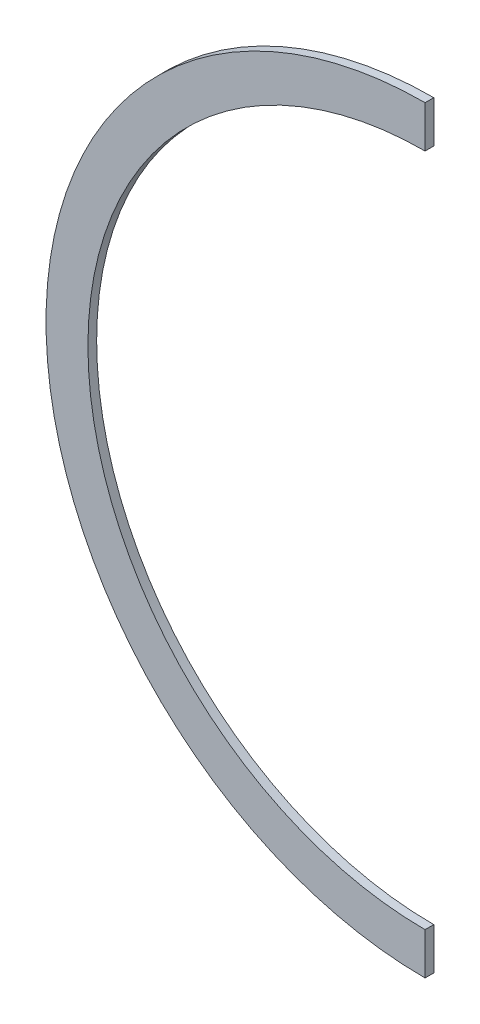
SolidWorks part; units mm, degrees
material "Balsa"
ref_plane "Front Plane" through (0, 0, 0) normal (0, 0, 1) x (1, 0, 0)
ref_plane "Top Plane" through (0, 0, 0) normal (0, 1, 0) x (1, 0, 0)
ref_plane "Right Plane" through (0, 0, 0) normal (1, 0, 0) x (0, 0, -1)
sketch "Sketch1" plane through (0, 0, 0) normal (0, 0, 1) x (1, 0, 0)
  line L0 (0, 0) -> (0, 499.9473) construction
  line L1 (0, -114.7984) -> (0, -129.4545) construction
  line L2 (0, -374.4718) -> (0, 404.2655) construction
  line L3 (-1.651, 142.9921) -> (-1.651, 150.6121) construction
  line L4 (1.651, 142.9921) -> (1.651, 150.6121) construction
  line L5 (-1.651, 142.9921) -> (1.651, 142.9921) construction
  line L6 (136.2041, -53.806) -> (0.0002, 24.7625) construction
  line L7 (-136.2076, -53.7991) -> (0.0002, 24.7625) construction
  line L8 (136.2041, -53.806) -> (0.0002, 24.7625) construction
  line L9 (-136.2076, -53.7991) -> (0.0002, 24.7625) construction
  line L10 (-125.0584, -45.4626) -> (-118.4576, -41.6554) construction
  line L11 (-123.6259, -48.4483) -> (-116.8078, -44.5157) construction
  line L12 (-118.4576, -41.6554) -> (-116.8078, -44.5157) construction
  line L13 (-124.1455, -48.7479) -> (-123.6847, -48.4822) construction
  line L14 (-123.6847, -48.4822) -> (-123.6259, -48.4483) construction
  line L15 (-125.7952, -45.8876) -> (-125.1113, -45.4931) construction
  line L16 (-125.1113, -45.4931) -> (-125.0584, -45.4626) construction
  line L17 (125.4797, -45.7137) -> (125.1075, -45.499) construction
  line L18 (123.8298, -48.5739) -> (123.6807, -48.488) construction
  line L19 (117.0223, -44.647) -> (118.6722, -41.7868) construction
  line L20 (123.6807, -48.488) -> (123.6228, -48.4545) construction
  line L21 (123.6228, -48.4545) -> (117.0223, -44.647) construction
  line L22 (125.1075, -45.499) -> (125.0554, -45.4689) construction
  line L23 (125.0554, -45.4689) -> (118.6722, -41.7868) construction
  line L24 (-107.079, -46.8884) -> (-120.3798, -54.5735)
  line L25 (-108.6638, -44.1348) -> (-121.9647, -51.8199)
  line L28 (-115.4206, -47.9666) -> (-121.9445, -51.7361) construction
  line L29 (-120.2754, -54.5131) -> (-108.646, -44.1245) construction
  line L30 (-114.4607, -49.3188) -> (-122.1124, -53.7399) construction
  line L31 (-113.7686, -50.8257) -> (-120.3665, -54.6379) construction
  line L32 (-115.4206, -47.9666) -> (-113.7686, -50.8257) construction
  line L33 (106.3137, -46.4532) -> (129.9098, -60.0883)
  line L34 (107.9004, -43.7007) -> (131.505, -57.3407)
  line L35 (129.9098, -60.0883) -> (131.505, -57.3407)
  line L36 (129.9098, -60.0883) -> (131.505, -57.3407) construction
  line L37 (107.9004, -43.7007) -> (131.505, -57.3407) construction
  line L38 (106.3137, -46.4532) -> (129.9098, -60.0883) construction
  line L39 (129.9098, -60.0883) -> (107.9004, -43.7007) construction
  line L40 (118.9051, -51.8945) -> (101.8722, -42.0519) construction
  line L41 (120.3631, -54.6438) -> (113.7655, -50.8313)
  line L42 (122.0152, -51.7848) -> (122.0057, -51.7794) construction
  line L43 (113.7655, -50.8313) -> (115.4176, -47.9723)
  line L44 (122.0057, -51.7794) -> (121.9413, -51.7421) construction
  line L45 (121.9413, -51.7421) -> (115.4176, -47.9723)
  line L46 (-108.6638, -44.1348) -> (-121.9647, -51.8199)
  line L47 (-107.079, -46.8884) -> (-120.3798, -54.5735)
  arc A0 (-1.651, 150.6121) -> (-125.0584, -45.4626) centre (0, 12.7) ccw
  circle A1 centre (0, 12.7) radius 120.904
  arc A2 (0, 150.622) -> (-1.651, 150.6121) centre (0, 12.7) ccw
  circle A3 centre (0, 12.7) radius 137.922 construction
  arc A4 (1.651, 150.6121) -> (0, 150.622) centre (0, 12.7) ccw
  arc A5 (-124.3508, -46.9604) -> (-123.6259, -48.4483) centre (0, 12.7) ccw
  arc A6 (-123.6259, -48.4483) -> (-121.9445, -51.7361) centre (0, 12.7) ccw
  arc A7 (-125.0584, -45.4626) -> (-124.3508, -46.9604) centre (0, 12.7) ccw
  arc A8 (124.3477, -46.9667) -> (125.0554, -45.4689) centre (0, 12.7) ccw
  arc A9 (125.0554, -45.4689) -> (1.651, 150.6121) centre (0, 12.7) ccw
  arc A10 (123.6228, -48.4545) -> (124.3477, -46.9667) centre (0, 12.7) ccw
  arc A11 (-121.9153, -51.7914) -> (-121.1641, -53.1919) centre (0, 12.7) ccw
  arc A12 (-120.3665, -54.6379) -> (120.3631, -54.6438) centre (0, 12.7) ccw
  arc A13 (-121.9445, -51.7361) -> (-121.9153, -51.7914) centre (0, 12.7) ccw
  arc A14 (-121.1641, -53.1919) -> (-120.3827, -54.6089) centre (0, 12.7) ccw
  arc A15 (-120.3827, -54.6089) -> (-120.397, -54.5834) centre (0, 12.7) ccw construction
  arc A16 (-120.397, -54.5834) -> (-120.3665, -54.6379) centre (0, 12.7) ccw construction
  arc A17 (120.3936, -54.5893) -> (121.0149, -53.4654) centre (0, 12.7) ccw construction
  arc A18 (121.9413, -51.7421) -> (123.6228, -48.4545) centre (0, 12.7) ccw
  arc A19 (120.3631, -54.6438) -> (120.3936, -54.5893) centre (0, 12.7) ccw construction
  arc A20 (121.0149, -53.4654) -> (121.9121, -51.7974) centre (0, 12.7) ccw construction
  arc A21 (121.9121, -51.7974) -> (121.9413, -51.7421) centre (0, 12.7) ccw construction
  spline S0 degree 3 poles (106.3137, -46.4532) (106.8426, -45.5357) (107.3715, -44.6182) (107.9004, -43.7007) knots 0 0 0 0 1 1 1 1 weights 1 1 1 1
  spline S1 degree 3 poles (-66.0123, 133.6164) (-70.0128, 131.4329) (-73.8716, 129.0699) (-81.3156, 123.9975) (-84.9009, 121.288) (-91.7995, 115.5249) (-95.113, 112.4712) (-99.0811, 108.4341) (-99.866, 107.6157) (-101.4182, 105.9565) (-102.1865, 105.1147) (-104.4569, 102.5643) (-105.9223, 100.8334) (-110.1768, 95.5512) (-115.4725, 88.2691) (-120.0285, 80.5179) (-123.1654, 74.5269) (-124.1643, 72.5002) (-125.5914, 69.415) (-126.0551, 68.3791) (-126.9587, 66.292) (-127.3989, 65.2397) (-129.5278, 59.9684) (-131.0098, 55.7) (-133.5456, 47.0638) (-134.5993, 42.696) (-136.2795, 33.8613) (-136.906, 29.3944) (-137.415, 23.7472) (-137.5031, 22.6146) (-137.6514, 20.3429) (-137.7116, 19.2049) (-137.8496, 15.7999) (-137.8852, 13.5361) (-137.8263, 6.7629) (-137.3062, -2.2197) (-135.9163, -11.1068) (-134.5433, -17.7359) (-134.0304, -19.9395) (-132.8922, -24.3345) (-132.2653, -26.5303) (-130.2347, -33.03) (-128.6774, -37.2656) (-126.1245, -43.2881) (-125.286, -45.1501) (-124.4066, -46.9926) knots 0 0 0 0 0.03125 0.03125 0.0625 0.0625 0.09375 0.09375 0.101563 0.101563 0.109375 0.109375 0.125 0.125 0.15625 0.1875 0.1875 0.203125 0.203125 0.210938 0.210938 0.21875 0.21875 0.25 0.25 0.28125 0.28125 0.3125 0.3125 0.320313 0.320313 0.328125 0.328125 0.34375 0.34375 0.375 0.40625 0.40625 0.421875 0.421875 0.4375 0.4375 0.46875 0.46875 0.48295 0.48295 0.48295 0.48295 construction
  spline S2 degree 3 poles (-1557.5256, 1030.3086) (-495.2142, -0.1753) (-82.1366, -210.7146) (81.4542, -98.9353) (85.033, -96.2237) (91.9188, -90.4573) (95.2258, -87.4025) (99.1858, -83.3647) (99.9691, -82.5461) (101.5182, -80.8868) (102.2849, -80.0449) (104.5506, -77.4941) (106.013, -75.7632) (110.2586, -70.4809) (112.9006, -66.8403) (117.8152, -59.3254) (120.0877, -55.4512) (123.2166, -49.4629) (124.2129, -47.4373) (125.6361, -44.3538) (126.0986, -43.3185) (126.9997, -41.2327) (127.4386, -40.181) (129.5618, -34.9121) (131.0396, -30.646) (133.5674, -22.0152) (134.6173, -17.6505) (136.2906, -8.8227) (136.914, -4.3596) (137.4197, 1.2823) (137.5071, 2.4139) (137.6542, 4.6834) (137.7138, 5.8206) (137.85, 9.2232) (137.8846, 11.4853) (137.8228, 18.2533) (137.2995, 27.2283) (135.9081, 36.1069) (134.5347, 42.7292) (134.0218, 44.9305) (132.8839, 49.3207) (132.2571, 51.5145) (130.2267, 58.0093) (128.67, 62.2416) (125.1615, 70.5162) (123.2097, 74.5586) (118.9108, 82.4534) (116.5637, 86.3058) (113.3753, 90.999) (112.7241, 91.9325) (111.3996, 93.7822) (110.7272, 94.697) (108.6802, 97.4113) (107.2757, 99.181) (102.9447, 104.3725) (96.8571, 110.9816) (90.1513, 116.9722) (84.8861, 121.2292) (83.0917, 122.6088) (80.3399, 124.6181) (79.4113, 125.2786) (77.543, 126.5731) (76.6028, 127.2075) (71.8708, 130.3161) (67.9881, 132.6004) (60.0328, 136.7739) (55.9603, 138.6631) (47.6249, 142.0446) (43.3619, 143.537) (37.9102, 145.1462) (36.8136, 145.4551) (34.6205, 146.0438) (33.5224, 146.3241) (30.2234, 147.1229) (28.0179, 147.5997) (21.3832, 148.8649) (16.9358, 149.4889) (7.993, 150.3014) (3.4975, 150.4899) (-3.2824, 150.4396) (-5.5486, 150.3672) (-10.0934, 150.1088) (-12.3559, 149.9236) (-19.101, 149.2046) (-23.5473, 148.5072) (-32.3412, 146.6856) (-36.6887, 145.5614) (-43.1354, 143.5526) (-45.2718, 142.8291) (-49.5193, 141.273) (-51.6323, 140.4395) (-274.1905, 46.1884) (-224.836, -608.7963) (101.1574, -1839.6029) knots -1.31339 -1.31339 -1.31339 -1.31339 0.03125 0.03125 0.0625 0.0625 0.09375 0.09375 0.101563 0.101563 0.109375 0.109375 0.125 0.125 0.15625 0.15625 0.1875 0.1875 0.203125 0.203125 0.210938 0.210938 0.21875 0.21875 0.25 0.25 0.28125 0.28125 0.3125 0.3125 0.320313 0.320313 0.328125 0.328125 0.34375 0.34375 0.375 0.40625 0.40625 0.421875 0.421875 0.4375 0.4375 0.46875 0.46875 0.5 0.5 0.53125 0.53125 0.539062 0.539062 0.546875 0.546875 0.5625 0.5625 0.59375 0.625 0.625 0.640625 0.640625 0.648437 0.648437 0.65625 0.65625 0.6875 0.6875 0.71875 0.71875 0.75 0.75 0.757812 0.757812 0.765625 0.765625 0.78125 0.78125 0.8125 0.8125 0.84375 0.84375 0.859375 0.859375 0.875 0.875 0.90625 0.90625 0.9375 0.9375 0.953125 0.953125 0.96875 0.96875 2.612134 2.612134 2.612134 2.612134 only from (66.1767, -108.566) to (-66.0123, 133.6164)
  spline S3 degree 3 poles (66.1767, -108.566) (70.1708, -106.3789) (74.0231, -104.0129) (81.4542, -98.9353) (85.033, -96.2237) (91.9188, -90.4573) (95.2258, -87.4025) (99.1858, -83.3647) (99.9691, -82.5461) (101.5182, -80.8868) (102.2849, -80.0449) (104.5506, -77.4941) (106.013, -75.7632) (110.2586, -70.4809) (112.9006, -66.8403) (117.8152, -59.3254) (120.0877, -55.4512) (123.2166, -49.4629) (124.2129, -47.4373) (125.6361, -44.3538) (126.0986, -43.3185) (126.9997, -41.2327) (127.4386, -40.181) (129.5618, -34.9121) (131.0396, -30.646) (133.5674, -22.0152) (134.6173, -17.6505) (136.2906, -8.8227) (136.914, -4.3596) (137.4197, 1.2823) (137.5071, 2.4139) (137.6542, 4.6834) (137.7138, 5.8206) (137.85, 9.2232) (137.8846, 11.4853) (137.8228, 18.2533) (137.2995, 27.2283) (135.9081, 36.1069) (134.5347, 42.7292) (134.0218, 44.9305) (132.8839, 49.3207) (132.2571, 51.5145) (130.2267, 58.0093) (128.67, 62.2416) (125.1615, 70.5162) (123.2097, 74.5586) (118.9108, 82.4534) (116.5637, 86.3058) (113.3753, 90.999) (112.7241, 91.9325) (111.3996, 93.7822) (110.7272, 94.697) (108.6802, 97.4113) (107.2757, 99.181) (102.9447, 104.3725) (96.8571, 110.9816) (90.1513, 116.9722) (84.8861, 121.2292) (83.0917, 122.6088) (80.3399, 124.6181) (79.4113, 125.2786) (77.543, 126.5731) (76.6028, 127.2075) (71.8708, 130.3161) (67.9881, 132.6004) (60.0328, 136.7739) (55.9603, 138.6631) (47.6249, 142.0446) (43.3619, 143.537) (37.9102, 145.1462) (36.8136, 145.4551) (34.6205, 146.0438) (33.5224, 146.3241) (30.2234, 147.1229) (28.0179, 147.5997) (21.3832, 148.8649) (16.9358, 149.4889) (7.993, 150.3014) (3.4975, 150.4899) (-3.2824, 150.4396) (-5.5486, 150.3672) (-10.0934, 150.1088) (-12.3559, 149.9236) (-19.101, 149.2046) (-23.5473, 148.5072) (-32.3412, 146.6856) (-36.6887, 145.5614) (-43.1354, 143.5526) (-45.2718, 142.8291) (-49.5193, 141.273) (-51.6323, 140.4395) (-57.9206, 137.7764) (-62.0153, 135.798) (-66.0123, 133.6164) knots 0 0 0 0 0.03125 0.03125 0.0625 0.0625 0.09375 0.09375 0.101563 0.101563 0.109375 0.109375 0.125 0.125 0.15625 0.15625 0.1875 0.1875 0.203125 0.203125 0.210938 0.210938 0.21875 0.21875 0.25 0.25 0.28125 0.28125 0.3125 0.3125 0.320313 0.320313 0.328125 0.328125 0.34375 0.34375 0.375 0.40625 0.40625 0.421875 0.421875 0.4375 0.4375 0.46875 0.46875 0.5 0.5 0.53125 0.53125 0.539062 0.539062 0.546875 0.546875 0.5625 0.5625 0.59375 0.625 0.625 0.640625 0.640625 0.648437 0.648437 0.65625 0.65625 0.6875 0.6875 0.71875 0.71875 0.75 0.75 0.757812 0.757812 0.765625 0.765625 0.78125 0.78125 0.8125 0.8125 0.84375 0.84375 0.859375 0.859375 0.875 0.875 0.90625 0.90625 0.9375 0.9375 0.953125 0.953125 0.96875 0.96875 1 1 1 1 construction
  spline S4 degree 3 poles (-124.4066, -46.9926) (-124.169, -47.4906) (-123.9283, -47.9871) (-123.6847, -48.4822) knots 0.48295 0.48295 0.48295 0.48295 0.486788 0.486788 0.486788 0.486788 construction
  spline S5 degree 3 poles (-123.6847, -48.4822) (-122.846, -50.1865) (-121.9718, -51.874) (-118.9108, -57.4955) (-116.5612, -61.3517) (-113.369, -66.0497) (-112.7169, -66.9844) (-111.3913, -68.8351) (-110.7184, -69.7503) (-108.6697, -72.4662) (-107.264, -74.2369) (-102.929, -79.4315) (-96.8353, -86.0447) (-90.1214, -92.0392) (-84.8493, -96.299) (-83.0524, -97.6795) (-80.2967, -99.6899) (-79.367, -100.3507) (-77.4971, -101.6451) (-76.5559, -102.2795) (-71.8198, -105.3881) (-67.9332, -107.6723) (-59.9695, -111.8452) (-55.8924, -113.7339) (-47.5468, -117.114) (-43.2782, -118.6053) (-37.8188, -120.2127) (-36.7216, -120.521) (-34.5268, -121.1085) (-33.4279, -121.3881) (-30.1264, -122.185) (-27.9191, -122.6605) (-21.2788, -123.9216) (-16.8274, -124.5426) (-7.8757, -125.3484) (-3.3755, -125.5332) (3.4122, -125.4766) (5.6812, -125.4019) (10.231, -125.1387) (12.493, -124.9512) (19.2413, -124.2249) (23.6899, -123.5224) (32.4889, -121.6898) (36.8393, -120.5597) (43.2904, -118.5412) (45.4283, -117.8143) (48.6163, -116.6419) (49.6759, -116.2374) (51.7885, -115.4006) (52.8426, -114.968) (58.0839, -112.7404) (62.1792, -110.755) (66.1767, -108.566) knots 0.486788 0.486788 0.486788 0.486788 0.5 0.5 0.53125 0.53125 0.539062 0.539062 0.546875 0.546875 0.5625 0.5625 0.59375 0.625 0.625 0.640625 0.640625 0.648437 0.648437 0.65625 0.65625 0.6875 0.6875 0.71875 0.71875 0.75 0.75 0.757812 0.757812 0.765625 0.765625 0.78125 0.78125 0.8125 0.8125 0.84375 0.84375 0.859375 0.859375 0.875 0.875 0.90625 0.90625 0.9375 0.9375 0.953125 0.953125 0.960937 0.960937 0.96875 0.96875 1 1 1 1 construction
  spline S6 degree 3 poles (-108.6638, -44.1348) (-108.1355, -45.0527) (-107.6073, -45.9705) (-107.079, -46.8884) knots 0 0 0 0 1 1 1 1 weights 1 1 1 1
  spline S7 degree 3 poles (-121.9647, -51.8199) (-121.4364, -52.7377) (-120.9081, -53.6556) (-120.3798, -54.5735) knots 0 0 0 0 1 1 1 1 weights 1 1 1 1
  spline S8 degree 3 poles (-893.3224, -1777.9831) (-225.0811, -622.1996) (441.4046, 533.9822) (1105.2914, 1689.1002) knots -629.182709 -629.182709 -629.182709 -629.182709 630.825898 630.825898 630.825898 630.825898 weights 1.000316 0.999894 0.999895 1.000316 only from (106.3137, -46.4532) to (107.9004, -43.7007)
  spline S9 degree 3 poles (-121.8597, -51.7592) (-121.5948, -52.2177) (-121.3299, -52.6762) (-121.065, -53.1347) knots 0 0 0 0 0.5 0.5 0.5 0.5 weights 1 1 1 1 construction
  spline S12 degree 3 poles (-1117.6926, 1681.4946) (-455.9021, 527.2867) (209.8433, -629.4163) (878.1921, -1786.2645) knots -630.157908 -630.157908 -630.157908 -630.157908 629.848871 629.848871 629.848871 629.848871 weights 1.000509 0.999831 0.99983 1.000507 only from (-121.9647, -51.8199) to (-120.3798, -54.5735)
  spline S13 degree 3 poles (-1104.4721, 1689.253) (-442.507, 534.8951) (223.2028, -621.8101) (891.4356, -1778.7423) knots -630.135261 -630.135261 -630.135261 -630.135261 629.876801 629.876801 629.876801 629.876801 weights 1.000459 0.999847 0.999847 1.000457 only from (-108.6638, -44.1348) to (-107.079, -46.8884)
  point P7 (0, -125.5003)
  point P8 (0, 150.4602)
  point P25 (-125.0584, -45.4626)
  point P38 (123.6228, -48.4545)
  dimension "D2" = 275.844
  dimension "D1" = 275.9605
  dimension "D3" = 12.7
  dimension "D5" = 3.302
  dimension "D6" = 7.62
  dimension "D7" = 3.302
  dimension "D8" = 7.62
  dimension "D9" = 3.302
  dimension "D10" = 7.62
  dimension "D11" = 3.302
  dimension "D12" = 7.62
  dimension "D13" = 3.302
  dimension "D14" = 7.62
  dimension "D4" = 17.018
extrude "Boss-Extrude1" [suppressed] add sketch "Sketch1" along normal mid plane 3.175
sketch "Sketch2" plane through (248.2736, -245.0135, 0) normal (0, 0, -1) x (0, -1, 0)
  line L3 (-245.0135, 248.2736) -> (-427.6569, 248.2736) construction
  circle A1 centre (-257.7135, 248.2736) radius 137.922
  circle A16 centre (-257.7135, 248.2736) radius 122.682
  dimension "D1" = 12.7
  dimension "D2" = 275.844
  dimension "D3" = 15.24
fillet "Fillet1" [suppressed] radius 1.27
extrude "Boss-Extrude2" add sketch "Sketch2" along normal mid plane 3.175
sketch "Sketch3" plane through (0, 0, 0) normal (1, 0, 0) x (0, 0, -1)
  line L1 (-141.282, 263.3615) -> (149.6958, 263.3615)
  line L2 (-141.282, 263.3615) -> (-141.282, -241.4673)
  line L3 (-141.282, -241.4673) -> (149.6958, -241.4673)
  line L4 (149.6958, 263.3615) -> (149.6958, -241.4673)
extrude "Cut-Extrude1" cut sketch "Sketch3" along normal through all
equation "\"slotwidth\"=0.13"
equation "\"D11@Sketch1\"=\"slotwidth\""
